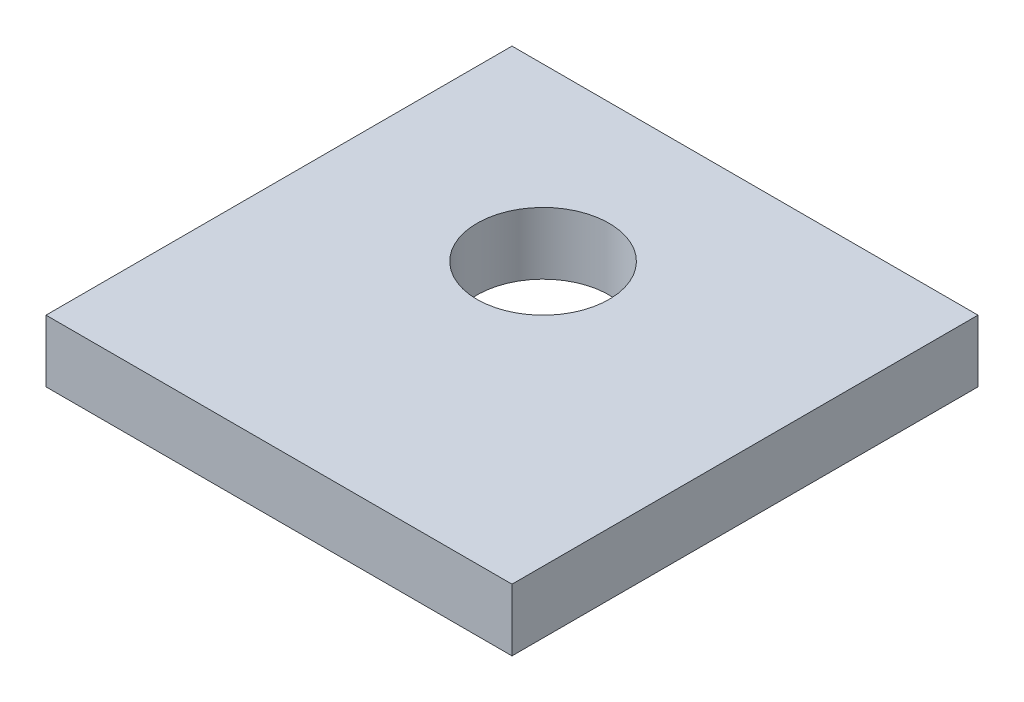
SolidWorks part; units mm, degrees
ref_plane "Front" through (0, 0, 0) normal (0, 0, 1) x (1, 0, 0)
ref_plane "Top" through (0, 0, 0) normal (0, 1, 0) x (1, 0, 0)
ref_plane "Right" through (0, 0, 0) normal (1, 0, 0) x (0, 0, -1)
sketch "Sketch1" plane through (0, 0, 0) normal (0, 1, 0) x (1, 0, 0)
  line L1 (-15, -15) -> (15, -15)
  line L2 (-15, -15) -> (-15, 15)
  line L3 (-15, 15) -> (15, 15)
  line L4 (15, -15) -> (15, 15)
  line L5 (-15, -15) -> (15, 15) construction
  line L6 (-15, 15) -> (15, -15) construction
  point P0 (0, 0)
  dimension "D1" = 30
  dimension "D2" = 30
extrude "Boss-Extrude1" add sketch "Sketch1" along normal mid plane 4
sketch "Sketch2" plane through (0, 2, 0) normal (0, 1, 0) x (1, 0, 0)
  circle A0 centre (-2, 4) radius 4.25
  circle A1 centre (-2, 4) radius 4 construction
  dimension "D1" = 8.5
extrude "Cut-Extrude1" cut sketch "Sketch2" against normal through all
